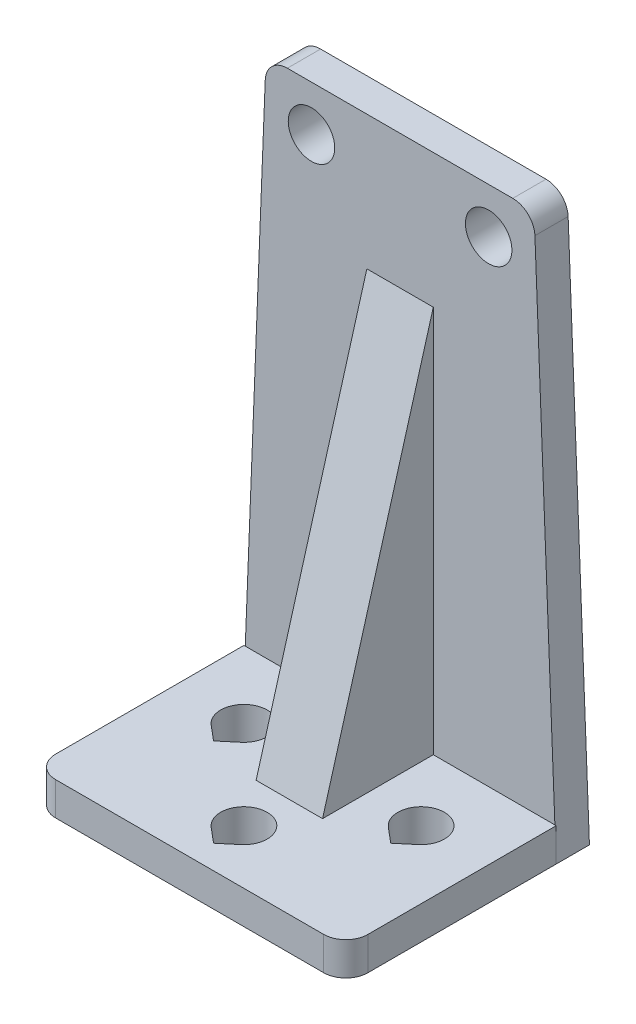
SolidWorks part; units mm, degrees
ref_plane "Front Plane" through (0, 0, 0) normal (0, 0, 1) x (1, 0, 0)
ref_plane "Top Plane" through (0, 0, 0) normal (0, 1, 0) x (1, 0, 0)
ref_plane "Right Plane" through (0, 0, 0) normal (1, 0, 0) x (0, 0, -1)
sketch "Sketch1" plane through (0, 0, 0) normal (0, 1, 0) x (1, 0, 0)
  line L0 (-8, -6.1) -> (8, -6.1) construction
  line L1 (-14.1, -19) -> (14.1, -19)
  line L2 (-14.1, -19) -> (-14.1, 0)
  line L3 (-14.1, 0) -> (14.1, 0)
  line L4 (14.1, -19) -> (14.1, 0)
  line L5 (-9.3499, -7.7087) -> (-8, -8.8414)
  line L6 (-8, -8.8414) -> (-6.6501, -7.7087)
  line L7 (-1.3499, -15.7087) -> (0, -16.8414)
  line L8 (0, -16.8414) -> (1.3499, -15.7087)
  line L9 (6.6501, -7.7087) -> (8, -8.8414)
  line L10 (8, -8.8414) -> (9.3499, -7.7087)
  arc A0 (-6.6501, -7.7087) -> (-9.3499, -7.7087) centre (-8, -6.1) ccw
  arc A1 (9.3499, -7.7087) -> (6.6501, -7.7087) centre (8, -6.1) ccw
  arc A2 (1.3499, -15.7087) -> (-1.3499, -15.7087) centre (0, -14.1) ccw
  point P4 (0, 0)
  point P10 (0, -6.1)
  dimension "D3" = 4.2
  dimension "D1" = 28.2
  dimension "D2" = 19
  dimension "D4" = 16
  dimension "D5" = 4
  dimension "D6" = 8
  dimension "D7" = 100
  dimension "D8" = 100
  dimension "D9" = 100
extrude "Boss-Extrude1" add sketch "Sketch1" along normal blind 3
sketch "Sketch2" plane through (0, 0, 0) normal (0, 0, -1) x (-1, 0, 0)
  line L0 (-8, 46) -> (8, 46) construction
  line L1 (-14.1, 0) -> (14.1, 0)
  line L2 (-14.1, 0) -> (-12.1, 50.1)
  line L3 (-12.1, 50.1) -> (12.1, 50.1)
  line L4 (14.1, 0) -> (12.1, 50.1)
  circle A0 centre (-8, 46) radius 2.1
  circle A1 centre (8, 46) radius 2.1
  point P5 (0, 46)
  point P12 (0, 50.1)
  dimension "D1" = 4.2
  dimension "D2" = 16
  dimension "D3" = 2
  dimension "D4" = 2
  dimension "D5" = 46
extrude "Boss-Extrude2" add sketch "Sketch2" along normal blind 3
sketch "Sketch3" plane through (0, 0, 0) normal (1, 0, 0) x (0, 0, -1)
  line L0 (0, 3) -> (-10, 3)
  line L1 (-19, 3) -> (0, 3) construction
  line L2 (-10, 3) -> (0, 38)
  line L3 (0, 50.1) -> (0, 3) construction
  line L4 (0, 38) -> (0, 3)
  dimension "D1" = 10
  dimension "D2" = 35
extrude "Boss-Extrude3" add sketch "Sketch3" along normal mid plane 6
fillet "Fillet1" radius 2 4 edges at (12.1, 50.1, -1.5) (-12.1, 50.1, -1.5) (14.1, 1.5, 19) (-14.1, 1.5, 19)
equation "\"width\"= 24"
equation "\"thk\"= 3"
equation "\"holesize\"= 4.2"
equation "\"holedistance\"= ( 20 + 12 ) / 2"
equation "\"threaded_hole\"= 3.9"
equation "\"fillet_radius\"= 2"
equation "\"ground_clearance\"= 25"
equation "\"tire_thk\"= 3"
equation "\"innerwheel_diam\" = \"wheel_diam\"-2*\"tire_thk\""
equation "\"innerwheel_thk\"= 8"
equation "\"wheel_diam\"= 2*(\"width\"/2+\"ground_clearance\")"
equation "\"coloursensor_holesize\"= 2.65"
equation "\"hole_to_edge\" = 4"
equation "\"D1@Sketch1\"=\"holedistance\"+ \"holesize\" + 2 * \"hole_to_edge\""
equation "\"D3@Sketch1\"=\"holesize\""
equation "\"D4@Sketch1\"=\"holedistance\""
equation "\"D6@Sketch1\"=\"holedistance\"/2"
equation "\"D5@Sketch1\"=\"hole_to_edge\""
equation "\"D1@Boss-Extrude1\"=\"thk\""
equation "\"D1@Sketch2\"=\"holesize\""
equation "\"D2@Sketch2\"=\"holedistance\""
equation "\"D4@Sketch2\"=\"D3@Sketch2\""
equation "\"D1@Boss-Extrude2\"=\"thk\""
equation "\"D1@Fillet1\"=\"fillet_radius\""
equation "\"D8@Sketch1\"=\"D7@Sketch1\""
equation "\"D9@Sketch1\"=\"D7@Sketch1\""
equation "\"D5@Sketch2\"=42 + \"thk\" + 1"
